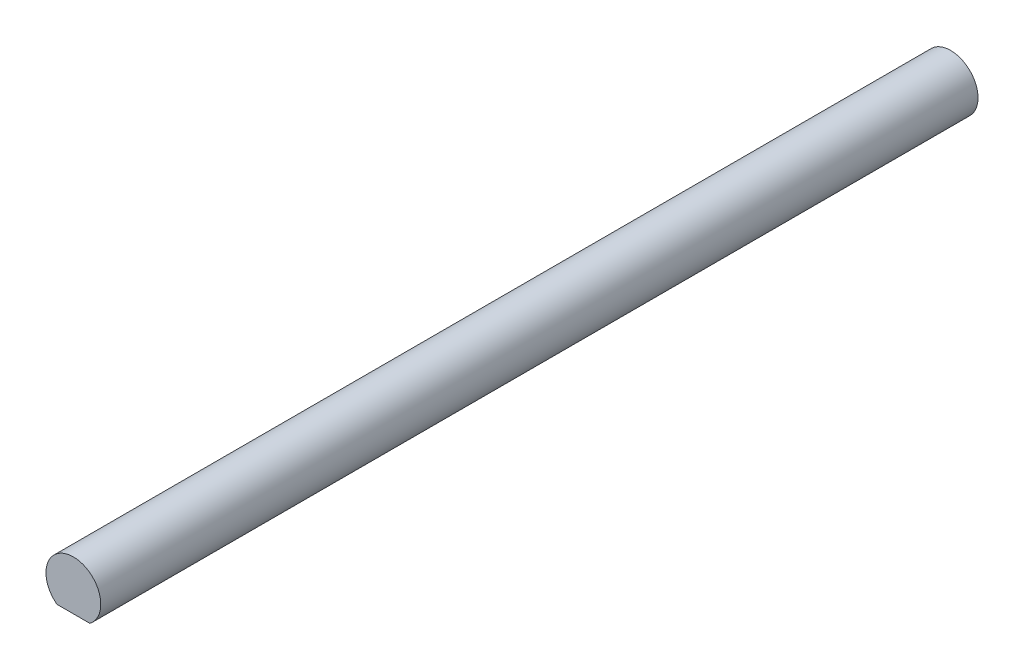
SolidWorks part; units mm, degrees
ref_plane "Front Plane" through (0, 0, 0) normal (0, 0, 1) x (1, 0, 0)
ref_plane "Top Plane" through (0, 0, 0) normal (0, 1, 0) x (1, 0, 0)
ref_plane "Right Plane" through (0, 0, 0) normal (1, 0, 0) x (0, 0, -1)
sketch "Sketch1" plane through (0, 0, 0) normal (0, 0, 1) x (1, 0, 0)
  line L0 (-1.905, -2.54) -> (1.905, -2.54)
  line L1 (0, 3.175) -> (0, -2.54) construction
  circle A0 centre (0, 0) radius 3.175
  dimension "D1" = 6.35
  dimension "D2" = 5.715
extrude "Boss-Extrude1" add sketch "Sketch1" along normal blind 50.8 and the other way blind 50.8 contours L1 A0 L0 | A0 L1 L0 region at (-1.3817, 0.1535, 0) region at (1.3817, 0.1535, 0)
ref_axis "Axis1" through (0, 0, -50.8) along (0, 0, 1)
